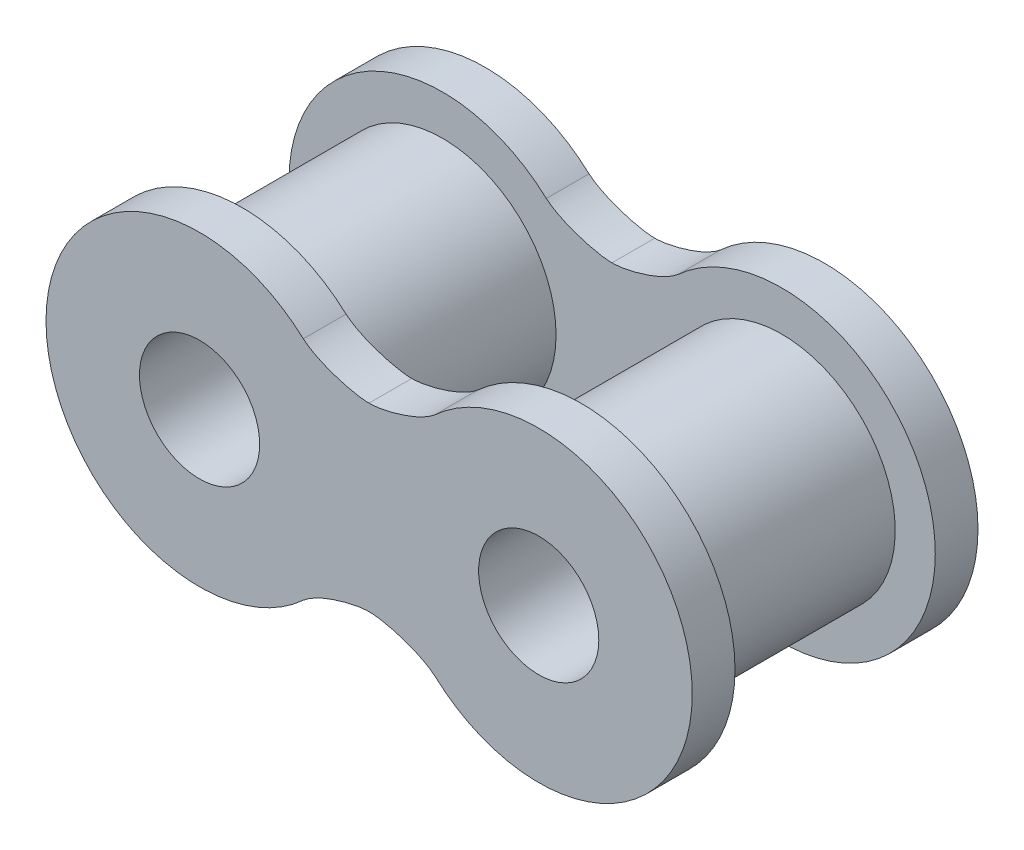
SolidWorks part; units mm, degrees
ref_plane "前视基准面" through (0, 0, 0) normal (0, 0, 1) x (1, 0, 0)
ref_plane "上视基准面" through (0, 0, 0) normal (0, 1, 0) x (1, 0, 0)
ref_plane "右视基准面" through (0, 0, 0) normal (1, 0, 0) x (0, 0, -1)
sketch "草图1" plane through (0, 0, 0) normal (0, 0, 1) x (1, 0, 0)
  line L0 (-6.35, 0) -> (66.7351, 0) construction
  line L1 (0, 69.5952) -> (0, 0) construction
  circle A0 centre (-6.35, 0) radius 4.25
  circle A1 centre (-6.35, 0) radius 2.25
  circle A2 centre (6.35, 0) radius 2.25
  circle A3 centre (6.35, 0) radius 4.25
  dimension "D1" = 4.5
  dimension "D2" = 8.5
  dimension "D3" = 12.7
extrude "凸台-拉伸1" add sketch "草图1" along normal blind 3.75
sketch "草图2" plane through (0, 0, 3.75) normal (0, 0, 1) x (1, 0, 0)
  line L0 (0, 35.0813) -> (0, 0) construction
  line L1 (-6.35, 0) -> (6.35, 0) construction
  circle A0 centre (-6.35, 0) radius 5.75
  circle A1 centre (6.35, 0) radius 5.75
  circle A2 centre (-6.35, 0) radius 2.25 construction
  circle A3 centre (-6.35, 0) radius 2.25
  circle A4 centre (6.35, 0) radius 2.25 construction
  circle A5 centre (6.35, 0) radius 2.25
  spline S0 degree 3 poles (-2.4645, 4.2386) (-1.8011, 3.6779) (-0.3708, 3.3459) (0, 3.3864) knots 0 0 0 0 1 1 1 1
  spline S1 degree 3 poles (2.4645, 4.2386) (1.8011, 3.6779) (0.3708, 3.3459) (0, 3.3864) knots 0 0 0 0 1 1 1 1
  spline S2 degree 3 poles (2.4645, -4.2386) (1.8011, -3.6779) (0.3708, -3.3459) (0, -3.3864) knots 0 0 0 0 1 1 1 1
  spline S3 degree 3 poles (-2.4645, -4.2386) (-1.8011, -3.6779) (-0.3708, -3.3459) (0, -3.3864) knots 0 0 0 0 1 1 1 1
  circle M5 centre (-6.35, 0) radius 4.25
  circle M6 centre (-6.35, 0) radius 2.25
  dimension "D1" = 11.5
extrude "凸台-拉伸3" add sketch "草图2" along normal blind 1.6 contours M5 M6 | A0 M5 | A0 S3 S2 A1 S1 S0 | A1 A5 region at (-1.2356, -2.2498, 3.75) region at (0, 0, 3.75) region at (8.5998, 5.1144, 3.75) region at (-10.4798, 0, 3.75)
ref_plane "基准面1" through (0, 0, 0) normal (0, 0, -1) x (-1, 0, 0)
mirror "镜向2" about plane through (0, 0, 0) normal (0, 0, -1) of "凸台-拉伸3", "凸台-拉伸1"
ref_plane "基准面2" through (0, 0, 0) normal (0, 0, 1) x (1, 0, 0)
